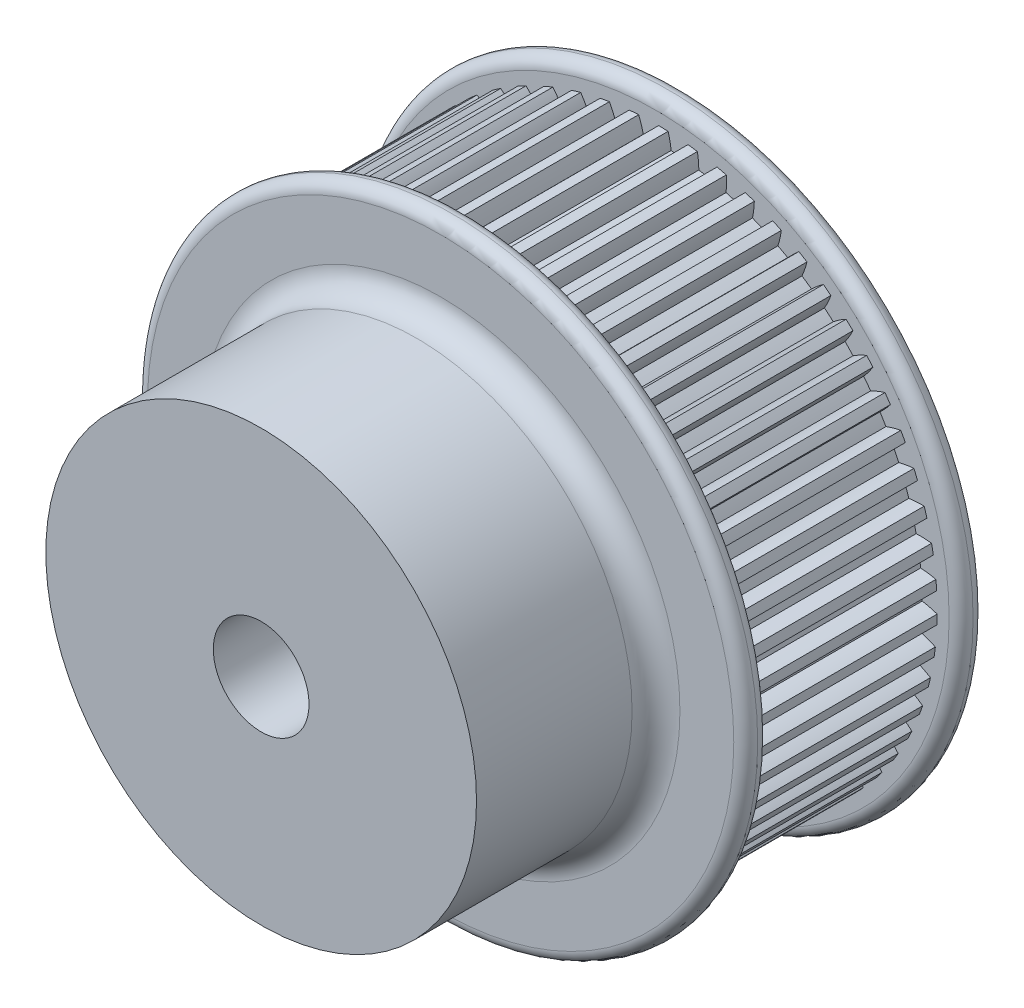
SolidWorks part; units mm, degrees
material "6061 Alloy"
ref_plane "Front Plane" through (0, 0, 0) normal (0, 0, 1) x (1, 0, 0)
ref_plane "Top Plane" through (0, 0, 0) normal (0, 1, 0) x (1, 0, 0)
ref_plane "Right Plane" through (0, 0, 0) normal (1, 0, 0) x (0, 0, -1)
sketch "Sketch1" plane through (0, 0, 0) normal (0, 0, 1) x (1, 0, 0)
  circle A0 centre (0, 0) radius 25.5
  circle A1 centre (0, 0) radius 4
  dimension "D1" = 51
  dimension "D2" = 8
extrude "Boss-Extrude1" add sketch "Sketch1" along normal blind 2
sketch "Sketch2" plane through (0, 0, 2) normal (0, 0, 1) x (1, 0, 0)
  line L0 (0, 0) -> (0, 22.316) construction
  line L1 (0, 0) -> (0.5777, 22.0617) construction
  line L2 (0, 23.5) -> (7.16, 21.0665) construction
  arc A0 (1.0115, 23.4782) -> (0, 23.5) centre (0, 0) ccw
  circle A1 centre (0, 0) radius 22.25
  circle A2 centre (0, 0) radius 22.75 construction
  circle A3 centre (0, 0) radius 4
  arc A4 (-0.0995, 22.2498) -> (0.2186, 23.499) centre (7.16, 21.0665) cw
  arc A5 (1.2638, 22.2141) -> (1.0115, 23.4782) centre (-6.0476, 21.4123) ccw
  point P13 (0, 22.75)
  dimension "D1" = 47
  dimension "D2" = 0.5
  dimension "D3" = 0.75
  dimension "D4" = 8
  dimension "D5" = 1.5
extrude "Boss-Extrude2" add sketch "Sketch2" along normal blind 16 contours A1 A3 | A1 A5 A0 A4 region at (0.5973, 22.8116, 2) region at (15.7163, 14.8476, 2)
sketch "Sketch3" plane through (0, 0, 0) normal (1, 0, 0) x (0, 0, -1)
  line L0 (0, 0) -> (-30.9332, 0) construction
pattern_circular "CirPattern1" count 60 over 360 about axis through (0, 0, 0) along (0, 0, 1) of "Boss-Extrude2"
sketch "Sketch4" plane through (0, 0, 18) normal (0, 0, 1) x (1, 0, 0)
  circle A0 centre (0, 0) radius 25.5
  circle A1 centre (0, 0) radius 4
  dimension "D1" = 8
  dimension "D2" = 51
extrude "Boss-Extrude3" add sketch "Sketch4" along normal blind 2
fillet "Fillet1" radius 1 4 edges at (25.5, 0, 0) (25.5, 0, 2) (25.5, 0, 18) (25.5, 0, 20)
sketch "Sketch5" plane through (0, 0, 0) normal (0, 0, -1) x (-1, 0, 0)
  circle A0 centre (0, 0) radius 18
  point P3 (-18, 0)
  point P4 (0, 18)
  point P5 (18, 0)
  point P6 (0, -18)
  dimension "D1" = 36
sketch "Sketch7" plane through (0, 0, 20) normal (0, 0, 1) x (1, 0, 0)
  circle A0 centre (0, 0) radius 18
  circle A1 centre (0, 0) radius 4
  dimension "D1" = 36
  dimension "D2" = 8
extrude "Boss-Extrude4" add sketch "Sketch7" along normal blind 15
fillet "Fillet2" radius 2 1 edges at (18, 0, 20)
